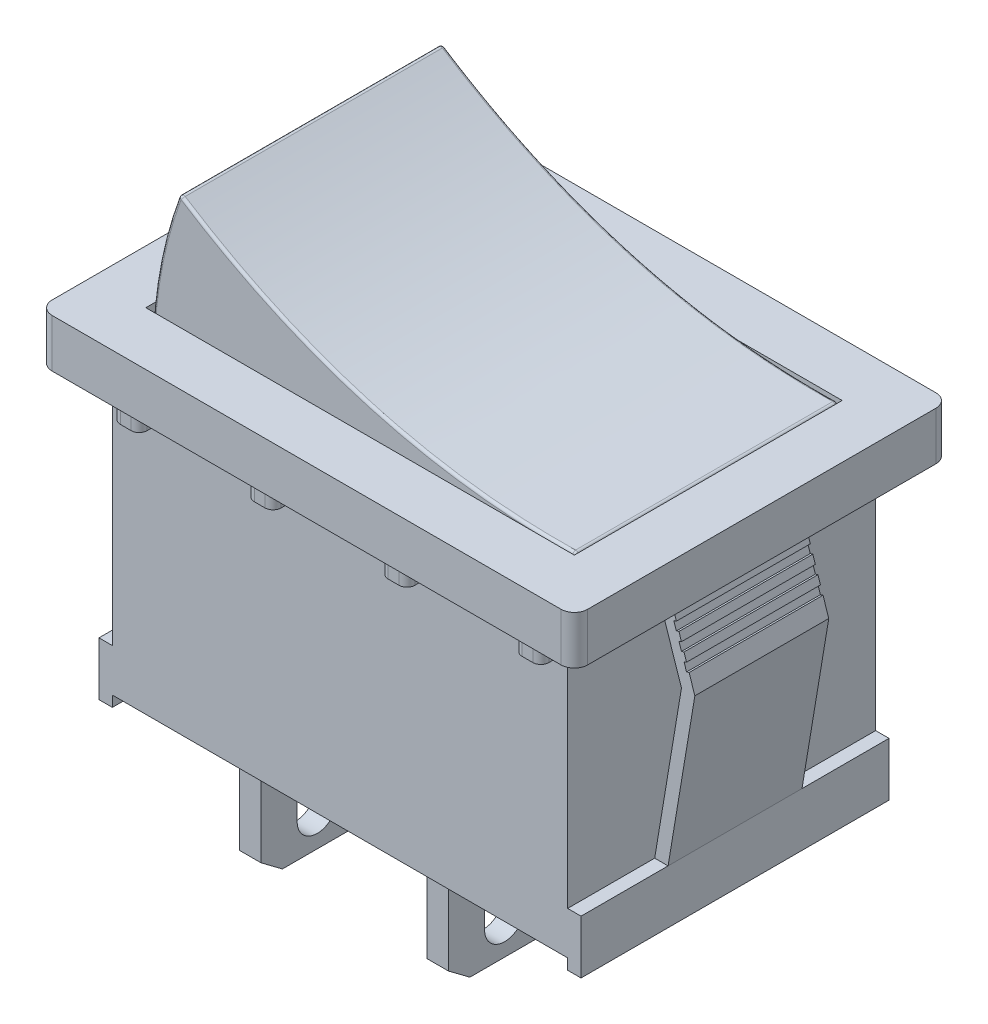
SolidWorks part; units mm, degrees
ref_plane "Alzado" through (0, 0, 0) normal (0, 0, 1) x (1, 0, 0)
ref_plane "Planta" through (0, 0, 0) normal (0, 1, 0) x (1, 0, 0)
ref_plane "Vista lateral" through (0, 0, 0) normal (1, 0, 0) x (0, 0, -1)
sketch "Croquis1" plane through (0, 0, 0) normal (0, 1, 0) x (1, 0, 0)
  line L1 (-9.5, -7) -> (9.5, -7)
  line L2 (-10, -6.5) -> (-10, 6.5)
  line L3 (-9.5, 7) -> (9.5, 7)
  line L4 (10, -6.5) -> (10, 6.5)
  line L5 (-10, -7) -> (10, 7) construction
  line L6 (-10, 7) -> (10, -7) construction
  arc A0 (-9.5, -7) -> (-10, -6.5) centre (-9.5, -6.5) cw
  arc A1 (9.5, -7) -> (10, -6.5) centre (9.5, -6.5) ccw
  arc A2 (9.5, 7) -> (10, 6.5) centre (9.5, 6.5) cw
  arc A3 (-10, 6.5) -> (-9.5, 7) centre (-9.5, 6.5) cw
  point P0 (0, 0)
  dimension "D3" = 0.5
  dimension "D1" = 20
  dimension "D2" = 14
extrude "Saliente-Extruir1" add sketch "Croquis1" along normal blind 1.8
sketch "Croquis2" plane through (0, 1.8, 0) normal (0, 1, 0) x (1, 0, 0)
  line L1 (-8, -5) -> (8, -5)
  line L2 (-8, -5) -> (-8, 5)
  line L3 (-8, 5) -> (8, 5)
  line L4 (8, -5) -> (8, 5)
  line L5 (-8, -5) -> (8, 5) construction
  line L6 (-8, 5) -> (8, -5) construction
  point P0 (0, 0)
  dimension "D1" = 10
  dimension "D2" = 16
extrude "Cortar-Extruir1" cut sketch "Croquis2" against normal blind 1.5
sketch "Croquis3" plane through (0, 0, 0) normal (0, 0, 1) x (1, 0, 0)
  line L0 (-7.875, 0.3) -> (8.0884, 0.3) construction
  line L6 (-0.5781, 0.3) -> (0, 0) construction
  line L8 (8.0469, 1.7936) -> (8.0884, 0.3)
  line L11 (0, 0) -> (0.5781, 0.3) construction
  line L13 (-9.5, 0) -> (9.5, 0) construction
  line L14 (8.0884, 0.3) -> (-7.875, 0.3)
  arc A0 (-6.834, 6) -> (-7.875, 0.3) centre (8.25, 0.3) ccw
  spline S0 degree 3 poles (-6.834, 6) (-2.2825, 3.0467) (2.6778, 1.6446) (8.0469, 1.7936) knots 0 0 0 0 0.987562 0.987562 0.987562 0.987562
  point P0 (0, 0)
  dimension "D3" = 32.25
  dimension "D2" = 0.3
  dimension "D4" = 6
extrude "Saliente-Extruir3" add sketch "Croquis3" along normal blind 4.9 and the other way blind 4.9
sketch "Croquis4" plane through (0, 1.8, 0) normal (0, 1, 0) x (1, 0, 0)
  line L0 (-8, -5) -> (8, -5) construction
  line L1 (8, 5) -> (7.95, 5)
  line L2 (8, 5) -> (8, -5)
  line L3 (8, -5) -> (7.95, -5)
  line L4 (7.95, 5) -> (7.95, -5)
  dimension "D1" = 0.05
extrude "Cortar-Extruir2" cut sketch "Croquis4" against normal blind 1.7
fillet "Redondeo1" radius 0.1 1 edges at (7.95, 1.7911, 0)
fillet "Redondeo2" radius 0.1 9 edges at (7.95, 0.9944, -4.9) (7.92, 1.7603, -4.9) (7.95, 0.9944, 4.9) (7.92, 1.7603, 4.9) (-7.6126, 3.1971, -4.9) (-6.834, 6, 0) (-7.6126, 3.1971, 4.9)
sketch "Croquis5" plane through (0, 0, 0) normal (0, -1, 0) x (1, 0, 0)
  line L1 (-8.5, -5.75) -> (8.5, -5.75)
  line L2 (-8.5, -5.75) -> (-8.5, 5.75)
  line L3 (-8.5, 5.75) -> (8.5, 5.75)
  line L4 (8.5, -5.75) -> (8.5, 5.75)
  line L5 (-8.5, -5.75) -> (8.5, 5.75) construction
  line L6 (-8.5, 5.75) -> (8.5, -5.75) construction
  point P0 (0, 0)
  dimension "D1" = 11.5
  dimension "D2" = 17
extrude "Saliente-Extruir4" add sketch "Croquis5" along normal blind 10.5
sketch "Croquis6" plane through (0, 0, 0) normal (0, -1, 0) x (1, 0, 0)
  line L0 (0, 7) -> (0, -7) construction
  line L1 (-9.5, 7) -> (9.5, 7) construction
  line L2 (9.5, -7) -> (-9.5, -7) construction
  line L3 (8.5, 5.75) -> (-8.5, 5.75) construction
  line L4 (2, 5.75) -> (3, 5.75)
  line L5 (2, 5.75) -> (2, 5.95)
  line L6 (2.3, 6.25) -> (2.7, 6.25)
  line L7 (3, 5.75) -> (3, 5.95)
  line L8 (7.3, 6.25) -> (7.7, 6.25)
  line L9 (8, 5.75) -> (8, 5.95)
  line L10 (7, 5.75) -> (7, 5.95)
  line L11 (7.3, 6.25) -> (7.7, 6.25)
  line L12 (8, 5.75) -> (8, 5.95)
  line L13 (7, 5.75) -> (7, 5.95)
  line L14 (-2.7, 6.25) -> (-2.3, 6.25)
  line L15 (-2, 5.75) -> (-2, 5.95)
  line L16 (-3, 5.75) -> (-3, 5.95)
  line L17 (-7.7, 6.25) -> (-7.3, 6.25)
  line L18 (-7, 5.75) -> (-7, 5.95)
  line L19 (-8, 5.75) -> (-8, 5.95)
  line L20 (-8.5, 0) -> (8.5, 0) construction
  line L21 (-8.5, 5.75) -> (-8.5, -5.75) construction
  line L22 (8.5, -5.75) -> (8.5, 5.75) construction
  line L23 (-8, -5.75) -> (-8, -5.95)
  line L24 (-7, -5.75) -> (-7, -5.95)
  line L25 (-7.7, -6.25) -> (-7.3, -6.25)
  line L26 (-3, -5.75) -> (-3, -5.95)
  line L27 (-2, -5.75) -> (-2, -5.95)
  line L28 (-2.7, -6.25) -> (-2.3, -6.25)
  line L29 (7, -5.75) -> (7, -5.95)
  line L30 (8, -5.75) -> (8, -5.95)
  line L31 (7.3, -6.25) -> (7.7, -6.25)
  line L32 (7, -5.75) -> (7, -5.95)
  line L33 (8, -5.75) -> (8, -5.95)
  line L34 (7.3, -6.25) -> (7.7, -6.25)
  line L35 (3, -5.75) -> (3, -5.95)
  line L36 (2.3, -6.25) -> (2.7, -6.25)
  line L37 (2, -5.75) -> (2, -5.95)
  line L38 (2, -5.75) -> (3, -5.75)
  arc A0 (2, 5.95) -> (2.3, 6.25) centre (2.3, 5.95) cw
  arc A1 (2.7, 6.25) -> (3, 5.95) centre (2.7, 5.95) cw
  arc A2 (7, 5.95) -> (7.3, 6.25) centre (7.3, 5.95) cw
  arc A3 (7, 5.95) -> (7.3, 6.25) centre (7.3, 5.95) cw
  arc A4 (7.7, 6.25) -> (8, 5.95) centre (7.7, 5.95) cw
  arc A5 (-3, 5.95) -> (-2.7, 6.25) centre (-2.7, 5.95) cw
  arc A6 (-2.3, 6.25) -> (-2, 5.95) centre (-2.3, 5.95) cw
  arc A7 (-8, 5.95) -> (-7.7, 6.25) centre (-7.7, 5.95) cw
  arc A8 (-7.3, 6.25) -> (-7, 5.95) centre (-7.3, 5.95) cw
  arc A9 (-7.3, -6.25) -> (-7, -5.95) centre (-7.3, -5.95) ccw
  arc A10 (-8, -5.95) -> (-7.7, -6.25) centre (-7.7, -5.95) ccw
  arc A11 (-2.3, -6.25) -> (-2, -5.95) centre (-2.3, -5.95) ccw
  arc A12 (-3, -5.95) -> (-2.7, -6.25) centre (-2.7, -5.95) ccw
  arc A13 (7.7, -6.25) -> (8, -5.95) centre (7.7, -5.95) ccw
  arc A14 (7, -5.95) -> (7.3, -6.25) centre (7.3, -5.95) ccw
  arc A15 (7, -5.95) -> (7.3, -6.25) centre (7.3, -5.95) ccw
  arc A16 (2.7, -6.25) -> (3, -5.95) centre (2.7, -5.95) ccw
  arc A17 (2, -5.95) -> (2.3, -6.25) centre (2.3, -5.95) ccw
  point P14 (2, 6.25)
  point P17 (3, 6.25)
  point P85 (3, -6.25)
  point P86 (2, -6.25)
  line M36 (-8.5, 5.75) -> (8.5, 5.75)
  line M38 (8.5, -5.75) -> (-8.5, -5.75)
  dimension "D3" = 0.3
  dimension "D1" = 1
  dimension "D2" = 2
  dimension "D4" = 0.5
  dimension "D7" = 3
  dimension "D5" = 2
  dimension "D6" = 2
extrude "Saliente-Extruir5" add sketch "Croquis6" along normal blind 1.2 contours A8 L17 A7 L19 L18 M36 | A6 L14 A5 L16 L15 M36 | A1 L6 A0 L5 L7 M36 | A4 L8 A2 L10 L9 M36 | L37 A17 L36 A16 L35 M38 | L29 A14 L31 A13 L30 M38 | L26 A12 L28 A11 L27 M38 | L23 A10 L25 A9 L24 M38 region at (2.5, 0, 5.9847) region at (7.5, 0, 5.9847) region at (-7.5, 0, 5.9847) region at (-2.5, 0, 5.9847) region at (-7.5, 0, -5.9847) region at (7.5, 0, -5.9847) region at (2.5, 0, -5.9847) region at (-2.5, 0, -5.9847)
sketch "Croquis7" plane through (8.5, 0, 0) normal (1, 0, 0) x (0, 0, -1)
  line L0 (-5.75, -10.5) -> (5.75, -10.5) construction
  line L1 (-5.75, -10.5) -> (-5.75, 0) construction
  line L2 (-5.75, -9) -> (5.75, -9)
  line L3 (-5.75, -9) -> (-5.75, -11)
  line L4 (-5.75, -11) -> (5.75, -11)
  line L5 (5.75, -9) -> (5.75, -11)
  dimension "D1" = 1.5
  dimension "D2" = 0.5
extrude "Saliente-Extruir6" add sketch "Croquis7" along normal blind 0.5
sketch "Croquis8" plane through (-8.5, 0, 0) normal (-1, 0, 0) x (0, 0, 1)
  line L0 (-5.75, -10.5) -> (5.75, -10.5) construction
  line L1 (-5.75, -10.5) -> (-5.75, 0) construction
  line L2 (-5.75, -9) -> (5.75, -9)
  line L3 (-5.75, -9) -> (-5.75, -11)
  line L4 (-5.75, -11) -> (5.75, -11)
  line L5 (5.75, -9) -> (5.75, -11)
  dimension "D1" = 1.5
extrude "Saliente-Extruir7" add sketch "Croquis8" along normal blind 0.5
sketch "Croquis9" plane through (0, -10.5, 0) normal (0, -1, 0) x (1, 0, 0)
  line L0 (-8.5, 0) -> (8.5, 0) construction
  line L1 (-8.5, 5.75) -> (-8.5, -5.75) construction
  line L2 (8.5, 5.75) -> (8.5, -5.75) construction
  line L3 (-9, -5.75) -> (-9, 5.75) construction
  line L4 (-7.4, -2.3) -> (-6.6, -2.3)
  line L5 (-7.4, -2.3) -> (-7.4, 2.3)
  line L6 (-7.4, 2.3) -> (-6.6, 2.3)
  line L7 (-6.6, -2.3) -> (-6.6, 2.3)
  line L8 (-7.4, -2.3) -> (-6.6, 2.3) construction
  line L9 (-7.4, 2.3) -> (-6.6, -2.3) construction
  line L11 (-0.4, -2.3) -> (0.4, -2.3)
  line L12 (-0.4, -2.3) -> (-0.4, 2.3)
  line L13 (-0.4, 2.3) -> (0.4, 2.3)
  line L14 (0.4, -2.3) -> (0.4, 2.3)
  line L15 (-0.4, -2.3) -> (0.4, 2.3) construction
  line L16 (-0.4, 2.3) -> (0.4, -2.3) construction
  point P6 (-7, 0)
  point P13 (0, 0)
  dimension "D1" = 0.8
  dimension "D2" = 4.6
  dimension "D3" = 1.6
  dimension "D4" = 0.8
  dimension "D5" = 7
extrude "Saliente-Extruir8" add sketch "Croquis9" along normal blind 7
sketch "Croquis10" plane through (-7.4, 0, 0) normal (-1, 0, 0) x (0, 0, 1)
  line L0 (0, -11) -> (0, -17.5) construction
  line L1 (-5.75, -11) -> (5.75, -11) construction
  line L2 (2.3, -17.5) -> (-2.3, -17.5) construction
  line L3 (0, -14.75) -> (0, -16.25) construction
  line L4 (0.75, -14.75) -> (0.75, -16.25)
  line L5 (-0.75, -14.75) -> (-0.75, -16.25)
  circle A0 centre (0, -12.2) radius 1
  arc A1 (0.75, -14.75) -> (-0.75, -14.75) centre (0, -14.75) ccw
  arc A2 (-0.75, -16.25) -> (0.75, -16.25) centre (0, -16.25) ccw
  point P10 (0, -15.5)
  dimension "D1" = 2
  dimension "D2" = 1.2
  dimension "D3" = 1.5
  dimension "D4" = 1.5
  dimension "D5" = 3.3
extrude "Cortar-Extruir3" cut sketch "Croquis10" against normal blind 10
sketch "Croquis11" plane through (-7.4, 0, 0) normal (-1, 0, 0) x (0, 0, 1)
  line L0 (0, -11) -> (0, -17.5) construction
  line L1 (-5.75, -11) -> (5.75, -11) construction
  line L2 (2.3, -17.5) -> (-2.3, -17.5) construction
  line L3 (-2.1, -11.9) -> (-2.1, -16.9)
  line L4 (2.1, -11.9) -> (2.1, -16.9)
  line L5 (-2.3, -17.5) -> (-2.3, -10.5) construction
  line L6 (2.3, -17.5) -> (2.3, -10.5) construction
  line L7 (-2.3, -11.8) -> (-2.2, -11.8)
  line L8 (2.2, -11.8) -> (2.3, -11.8)
  line L9 (-2.3, -11.8) -> (-2.3, -17.5)
  line L10 (-2.3, -17.5) -> (-2.1, -17.5)
  line L11 (2.3, -17.5) -> (2.3, -11.8)
  line L12 (2.1, -17.5) -> (2.3, -17.5)
  line L13 (-1.3, -11) -> (-1.3, -17.5) construction
  line L14 (1.3, -11) -> (1.3, -17.5) construction
  line L15 (1.3, -17.5) -> (2.1, -17.5)
  line L16 (1.3, -17.5) -> (2.1, -16.9)
  line L17 (-2.1, -17.5) -> (-1.3, -17.5)
  line L18 (-1.3, -17.5) -> (-2.1, -16.9)
  arc A0 (2.2, -11.8) -> (2.1, -11.9) centre (2.2, -11.9) ccw
  arc A1 (-2.2, -11.8) -> (-2.1, -11.9) centre (-2.2, -11.9) cw
  dimension "D5" = 0.1
  dimension "D1" = 0.2
  dimension "D2" = 0.2
  dimension "D3" = 0.8
  dimension "D4" = 0.8
  dimension "D6" = 0.8
  dimension "D7" = 0.8
  dimension "D8" = 1
  dimension "D9" = 1
extrude "Cortar-Extruir4" cut sketch "Croquis11" against normal blind 10
sketch "Croquis12" plane through (0, -10.5, 0) normal (0, -1, 0) x (1, 0, 0)
  line L0 (-6.6, 2.3) -> (0.4, 2.3) construction
  line L1 (8.5, -5.75) -> (8.5, 5.75) construction
  line L2 (-8.5, 5.75) -> (8.5, 5.75)
  line L3 (-8.5, 5.75) -> (-8.5, 2.3)
  line L4 (-8.5, 2.3) -> (8.5, 2.3)
  line L5 (8.5, 5.75) -> (8.5, 2.3)
extrude "Saliente-Extruir9" add sketch "Croquis12" along normal blind 0.1
sketch "Croquis13" plane through (0, 0, 0) normal (0, 0, 1) x (1, 0, 0)
  line L0 (0, 0) -> (0, -10.6) construction
  line L1 (-0.4, -10.6) -> (0.4, -10.6) construction
  line L3 (8.5, 0) -> (9, 0)
  line L4 (-9.5, 0) -> (9.5, 0) construction
  line L5 (8.5, -9) -> (9.5, -3)
  line L6 (9.5, -3) -> (8.5, 0)
  line L7 (8.5, -9) -> (8.5, 0) construction
  line L8 (9, 0) -> (10, -3)
  line L9 (10, -3) -> (9, -9)
  line L10 (-10, -3) -> (-9, -9)
  line L11 (-9, 0) -> (-10, -3)
  line L12 (-9.5, -3) -> (-8.5, 0)
  line L13 (-8.5, -9) -> (-9.5, -3)
  line L14 (-8.5, 0) -> (-9, 0)
  line L15 (8.5, -9) -> (9, -9)
  line L16 (-8.5, -9) -> (-9, -9)
  dimension "D1" = 0.5
  dimension "D2" = 3
  dimension "D3" = 1
extrude "Saliente-Extruir10" add sketch "Croquis13" along normal blind 2.5 and the other way blind 2.5
sketch "Croquis14" plane through (8.1, 2.7, 0) normal (0.9487, 0.3162, 0) x (0, 0, -1)
  line L0 (-2.5, -4.4272) -> (2.5, -4.4272) construction
  line L1 (-2.5, -6.0083) -> (-2.5, -2.846) construction
  line L2 (2.5, -6.0083) -> (2.5, -2.846) construction
  line L3 (-2.5, -4.1272) -> (2.5, -4.1272)
  line L4 (-2.5, -3.8272) -> (2.5, -3.8272)
  line L5 (-2.5, -3.5272) -> (2.5, -3.5272)
  line L6 (-2.5, -4.4272) -> (2.5, -4.4272)
  line L7 (-2.5, -4.7272) -> (2.5, -4.7272)
  line L8 (-2.5, -5.0272) -> (2.5, -5.0272)
  line L9 (-2.5, -5.3272) -> (2.5, -5.3272)
  line L10 (-2.5, -3.8272) -> (-2.5, -4.1272)
  line L11 (2.5, -3.8272) -> (2.5, -4.1272)
  line L12 (-2.5, -5.0272) -> (-2.5, -5.3272)
  line L13 (2.5, -5.0272) -> (2.5, -5.3272)
  line L14 (2.5, -4.4272) -> (2.5, -4.7272)
  line L15 (-2.5, -4.4272) -> (-2.5, -4.7272)
  line L16 (-2.5, -3.2272) -> (2.5, -3.2272)
  line L17 (-2.5, -3.5272) -> (-2.5, -3.2272)
  line L18 (2.5, -3.5272) -> (2.5, -3.2272)
  dimension "D1" = 0.3
  dimension "D2" = 0.3
  dimension "D3" = 0.3
  dimension "D4" = 0.3
  dimension "D5" = 0.3
  dimension "D6" = 0.3
  dimension "D7" = 0.3
extrude "Cortar-Extruir5" cut sketch "Croquis14" against normal blind 0.1
mirror "Simetría1" about plane through (0, 0, 0) normal (1, 0, 0) of "Cortar-Extruir5"
